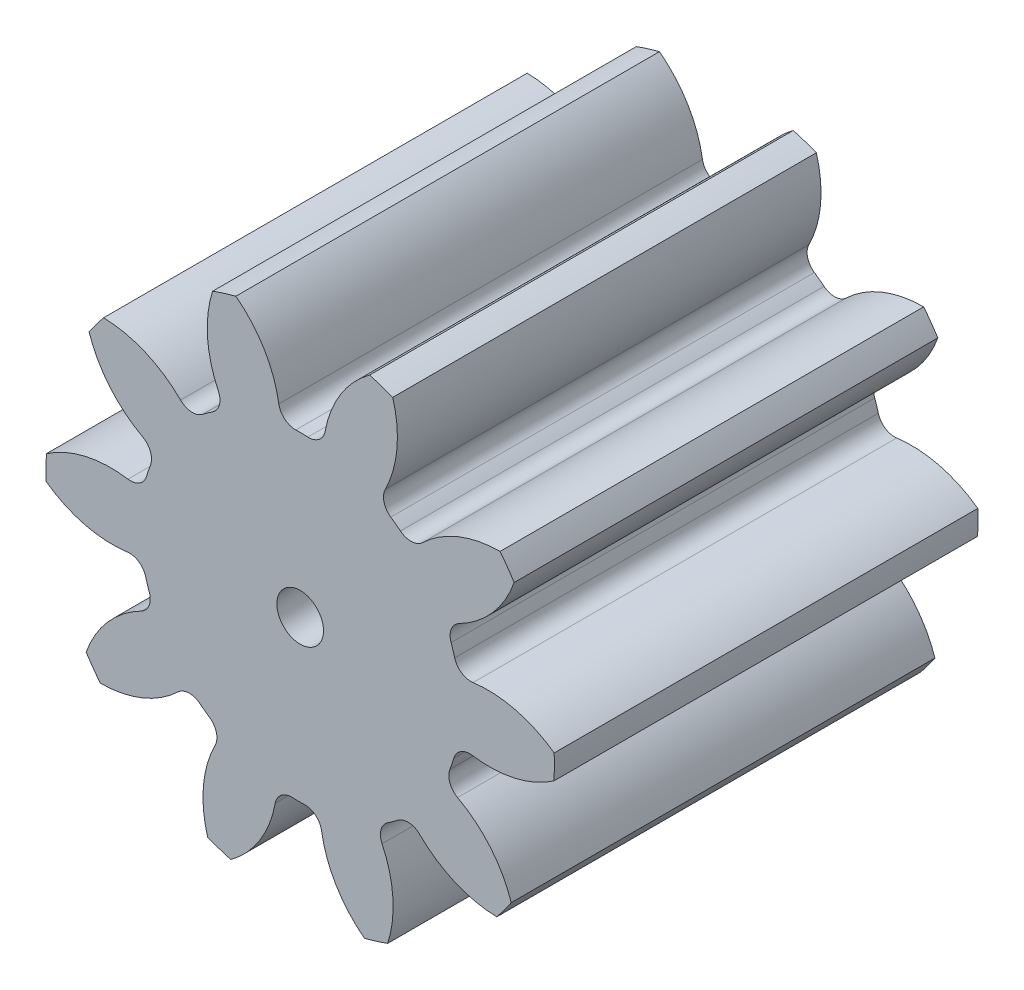
SolidWorks part; units mm, degrees
ref_plane "Front" through (0, 0, 0) normal (0, 0, 1) x (1, 0, 0)
ref_plane "Top" through (0, 0, 0) normal (0, 1, 0) x (1, 0, 0)
ref_plane "Right" through (0, 0, 0) normal (1, 0, 0) x (0, 0, -1)
sketch "Sketch3" plane through (0, 0, 0) normal (0, 0, 1) x (1, 0, 0)
  circle A0 centre (0, 0) radius 15.24
  dimension "od" = 30.48
extrude "gearBody" add sketch "Sketch3" along normal blind 25.4
sketch "Sketch2" plane through (0, 0, 0) normal (0, 0, 1) x (1, 0, 0)
  line L0 (0, 0) -> (11.3595, 4.7053) construction
  line L1 (12.8367, -12.0857) -> (0, 0) construction
  line L2 (0, 0) -> (36.3143, 0) construction
  line L3 (12.544, -1.9847) -> (11.1917, -6.003) construction
  line L5 (11.8678, -3.9939) -> (0, 0) construction
  line L7 (0, 0) -> (12.2955, 0) construction
  arc A0 (12.1241, -2.0456) -> (10.8941, -5.7007) centre (0, 0) ccw construction
  arc A1 (15.214, -0.8896) -> (12.6563, -8.4897) centre (0, 0) ccw construction
  arc A2 (12.544, -1.9847) -> (11.1917, -6.003) centre (0, 0) ccw construction
  arc A3 (8.9781, -3.4023) -> (9.2084, -2.718) centre (0, 0) ccw
  arc A4 (12.8367, -12.0857) -> (9.4391, -4.6417) centre (6.2035, -10.6158) ccw
  arc A5 (12.8367, -12.0857) -> (17.5318, 1.8658) centre (0, 0) ccw
  arc A6 (17.5318, 1.8658) -> (10.3249, -2.0095) centre (11.3595, 4.7053) cw
  arc A7 (9.2084, -2.718) -> (10.3249, -2.0095) centre (10.1719, -3.0024) cw
  arc A8 (9.4391, -4.6417) -> (8.9781, -3.4023) centre (9.9175, -3.7583) cw
  point P6 (17.5318, 1.8658)
  point P22 (12.8367, -12.0857)
  dimension "baseDia" = 24.591
  dimension "od" = 30.48
  dimension "pd" = 25.4
  dimension "rd" = 19.2024
  dimension "rFillet" = 1.0046
  dimension "pointX" = 17.5318
  dimension "pointY" = 1.8658
  dimension "CTT" = 4.0183
  dimension "flankCenterAngle" = 22.5
extrude "toothCut" cut sketch "Sketch2" along normal through all
pattern_circular "CirPattern1" count 10 over 360 about axis through (0, 0, 25.4) along (0, 0, -1) of "toothCut"
ref_axis "toothSpace" through (0, 0, 0) along (0.9478, -0.319, 0)
ref_axis "Axis2" through (12.235, -9.0864, 0) along (-0.8028, 0.5962, 0)
sketch "hub1Dia" plane through (0, 0, 0) normal (0, 0, -1) x (-1, 0, 0)
  circle A0 centre (0, 0) radius 12.7
  dimension "hub1Dia" = 25.4
sketch "hub2Dia" plane through (0, 0, 25.4) normal (0, 0, 1) x (1, 0, 0)
  circle A0 centre (0, 0) radius 12.7
  dimension "hub2dia" = 25.4
sketch "boreDia" plane through (0, 0, 0) normal (0, 0, 1) x (1, 0, 0)
  circle A0 centre (0, 0) radius 1.397
  dimension "boreDia" = 2.794
extrude "bore" cut sketch "boreDia" against normal mid plane 25400
sketch "kwy1sketch" plane through (0, 0, 0) normal (0, 0, 1) x (1, 0, 0)
  line L0 (-4.3738, 2.5866) -> (0, 0) construction
  line L1 (29.5301, -2.7092) -> (16.6006, -24.5721)
  line L2 (16.6006, -24.5721) -> (-10.728, -8.4102)
  line L3 (29.5301, -2.7092) -> (2.2015, 13.4527)
  line L4 (-10.728, -8.4102) -> (0, 0)
  line L5 (0, 0) -> (2.2015, 13.4527)
  line L6 (0, 0) -> (9.0997, -3.0623) construction
  line L7 (23.0654, -13.6406) -> (0, 0) construction
  arc A7 (8.9781, -3.4023) -> (9.2084, -2.718) centre (0, 0) ccw construction
  point P9 (23.0654, -13.6406)
  point P13 (-0.7296, 0.4315)
  dimension "kwy1width" = 25.4
  dimension "kwy1depth" = 26.797
  dimension "kwy1angle" = 12
  dimension "kwy1Depth2" = 31.75
sketch "kwy2sketch" plane through (0, 0, 0) normal (0, 0, 1) x (1, 0, 0)
  line L0 (9.0997, -3.0623) -> (0, 0) construction
  line L1 (0, 0) -> (-3.4011, -0.8733) construction
  line L2 (22.7966, 18.9653) -> (29.1135, -5.6367)
  line L3 (29.1135, -5.6367) -> (-1.6389, -13.5328)
  line L4 (22.7966, 18.9653) -> (-7.9558, 11.0692)
  line L5 (-1.6389, -13.5328) -> (0, 0)
  line L6 (0, 0) -> (-7.9558, 11.0692)
  arc A2 (8.9781, -3.4023) -> (9.2084, -2.718) centre (0, 0) ccw construction
  point P10 (25.9551, 6.6643)
  dimension "kwy2angle" = 33
  dimension "kwy2Width" = 25.4
  dimension "kwy2depth" = 26.797
  dimension "kwy2Depth2" = 31.75
sketch "kwy3sketch" plane through (0, 0, 0) normal (0, 0, 1) x (1, 0, 0)
  line L0 (9.0997, -3.0623) -> (0, 0) construction
  line L1 (0, 0) -> (-1.2931, -2.1866) construction
  line L2 (2.7092, 29.5301) -> (24.5721, 16.6006)
  line L3 (24.5721, 16.6006) -> (8.4102, -10.728)
  line L4 (2.7092, 29.5301) -> (-13.4527, 2.2015)
  line L5 (8.4102, -10.728) -> (0, 0)
  line L6 (-13.4527, 2.2015) -> (0, 0)
  point P10 (13.6406, 23.0654)
  dimension "kwy3angle" = 78
  dimension "kwy3depth" = 26.797
  dimension "kwy3width" = 25.4
  dimension "kwy3Depth2" = 31.75
sketch "kwy4sketch" plane through (0, 0, 0) normal (0, 0, 1) x (1, 0, 0)
  line L0 (9.0997, -3.0623) -> (0, 0) construction
  line L1 (0, 0) -> (0.494, -1.9239) construction
  line L2 (5.6367, 29.1135) -> (-18.9653, 22.7966)
  line L3 (-18.9653, 22.7966) -> (-11.0692, -7.9558)
  line L4 (-11.0692, -7.9558) -> (0, 0)
  line L5 (13.5328, -1.6389) -> (0, 0)
  line L6 (5.6367, 29.1135) -> (13.5328, -1.6389)
  point P15 (-6.6643, 25.9551)
  dimension "kwy4angle" = 123
  dimension "kwy4depth" = 26.797
  dimension "kwy4width" = 25.4
  dimension "kwy4Depth2" = 31.75
sketch "kwy5sketch" plane through (0, 0, 0) normal (0, 0, 1) x (1, 0, 0)
  line L0 (9.0997, -3.0623) -> (0, 0) construction
  line L1 (0, 0) -> (1.4683, -0.8684) construction
  line L2 (-16.6006, 24.5721) -> (-29.5301, 2.7092)
  line L3 (-29.5301, 2.7092) -> (-2.2015, -13.4527)
  line L4 (-16.6006, 24.5721) -> (10.728, 8.4102)
  line L5 (-2.2015, -13.4527) -> (0, 0)
  line L6 (10.728, 8.4102) -> (0, 0)
  point P10 (-23.0654, 13.6406)
  dimension "kwy5width" = 25.4
  dimension "kwy5depth" = 26.797
  dimension "kwy5angle" = 168
  dimension "kwy5Depth2" = 31.75
sketch "kwy6sketch" plane through (0, 0, 0) normal (0, 0, 1) x (1, 0, 0)
  line L0 (9.0997, -3.0623) -> (0, 0) construction
  line L1 (0, 0) -> (1.651, 0.4239) construction
  line L2 (-29.1135, 5.6367) -> (-22.7966, -18.9653)
  line L3 (-22.7966, -18.9653) -> (7.9558, -11.0692)
  line L4 (-29.1135, 5.6367) -> (1.6389, 13.5328)
  line L5 (7.9558, -11.0692) -> (0, 0)
  line L6 (1.6389, 13.5328) -> (0, 0)
  point P10 (-25.9551, -6.6643)
  dimension "kwy6angle" = 213
  dimension "kwy6width" = 25.4
  dimension "kwy6depth" = 26.797
  dimension "kwy6Depth2" = 31.75
sketch "kwy7sketch" plane through (0, 0, 0) normal (0, 0, 1) x (1, 0, 0)
  line L0 (9.0997, -3.0623) -> (0, 0) construction
  line L1 (0, 0) -> (0.9721, 1.6437) construction
  line L2 (-24.5721, -16.6006) -> (-2.7092, -29.5301)
  line L3 (-24.5721, -16.6006) -> (-8.4102, 10.728)
  line L4 (-2.7092, -29.5301) -> (13.4527, -2.2015)
  line L5 (-8.4102, 10.728) -> (0, 0)
  line L6 (13.4527, -2.2015) -> (0, 0)
  point P10 (-13.6406, -23.0654)
  dimension "kwy7angle" = 78
  dimension "kwy7width" = 25.4
  dimension "kwy7depth" = 26.797
  dimension "kwy7angle1" = 258
  dimension "kwy7Depth2" = 31.75
sketch "kwy8sketch" plane through (0, 0, 0) normal (0, 0, 1) x (1, 0, 0)
  line L0 (9.0997, -3.0623) -> (0, 0) construction
  line L1 (0, 0) -> (-0.4219, 1.6433) construction
  line L2 (-5.6367, -29.1135) -> (18.9653, -22.7966)
  line L3 (18.9653, -22.7966) -> (11.0692, 7.9558)
  line L4 (-5.6367, -29.1135) -> (-13.5328, 1.6389)
  line L5 (11.0692, 7.9558) -> (0, 0)
  line L6 (-13.5328, 1.6389) -> (0, 0)
  point P10 (6.6643, -25.9551)
  dimension "kwy8angle" = 303
  dimension "kwy8width" = 25.4
  dimension "kwy8depth" = 26.797
  dimension "kwy8Depth2" = 31.75
sketch "centerLine" plane through (0, 0, 0) normal (0, 1, 0) x (1, 0, 0)
  line L0 (0, 36.4807) -> (0, -59.6309) construction
ref_plane "CB1plane" through (0, 0, 0) normal (0, 0, -1) x (-1, 0, 0)
sketch "CB1diameter" plane through (0, 0, 0) normal (0, 0, -1) x (-1, 0, 0)
  circle A0 centre (0, 0) radius 12.7
  dimension "CB1diameter" = 25.4
ref_plane "CB2plane" through (0, 0, 25.4) normal (0, 0, 1) x (1, 0, 0)
sketch "CB2diameter" plane through (0, 0, 25.4) normal (0, 0, 1) x (1, 0, 0)
  circle A0 centre (0, 0) radius 12.7
  dimension "CB2diameter" = 25.4
ref_axis "Axis1" through (0, 0, 50) along (0, 0, -1)
sketch3d "3DSketch1" plane through (0, 0, 0) normal (0, 0, 1) x (1, 0, 0)
